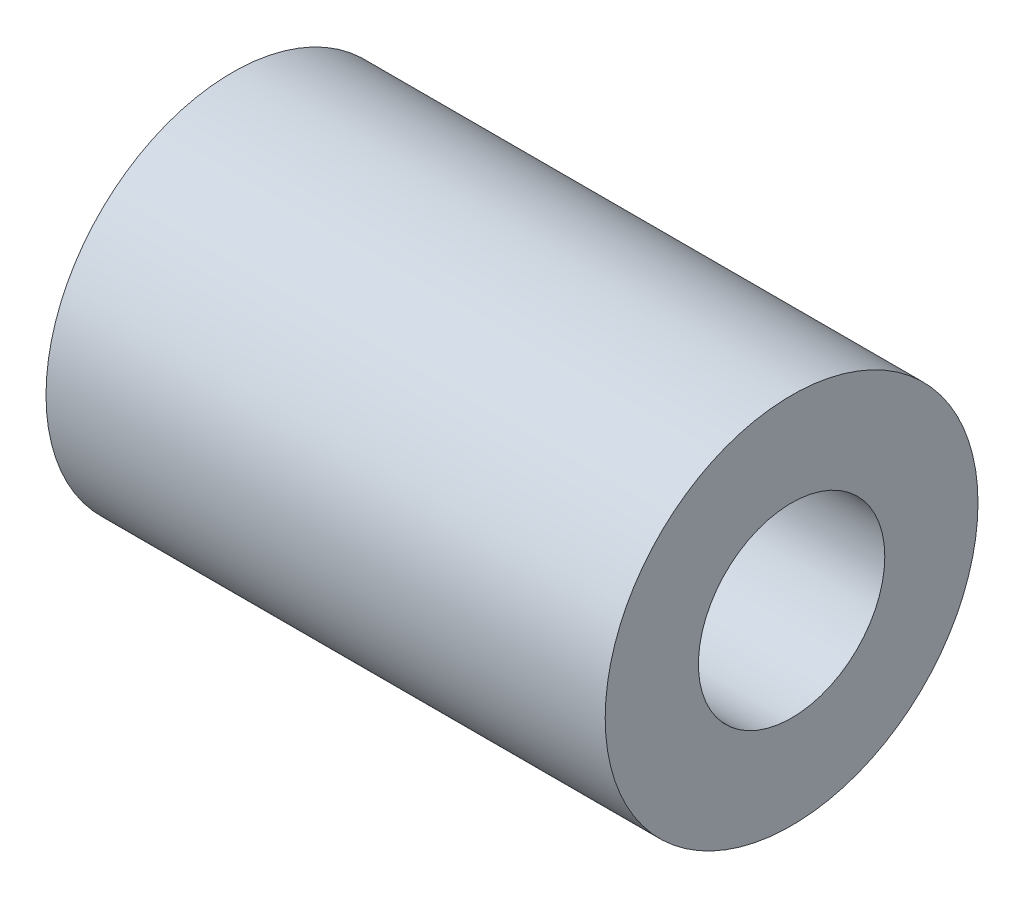
SolidWorks part; units mm, degrees
material "ABS"
ref_plane "Front" through (0, 0, 0) normal (0, 0, 1) x (1, 0, 0)
ref_plane "Top" through (0, 0, 0) normal (0, 1, 0) x (1, 0, 0)
ref_plane "Right" through (0, 0, 0) normal (1, 0, 0) x (0, 0, -1)
sketch "Szkic1" plane through (0, 0, 0) normal (1, 0, 0) x (0, 0, -1)
  circle A0 centre (0, 0) radius 2.5
  circle A1 centre (0, 0) radius 5
  dimension "D1" = 5
  dimension "D2" = 10
extrude "Dodanie-wyciągnięcie1" add sketch "Szkic1" along normal blind 15
